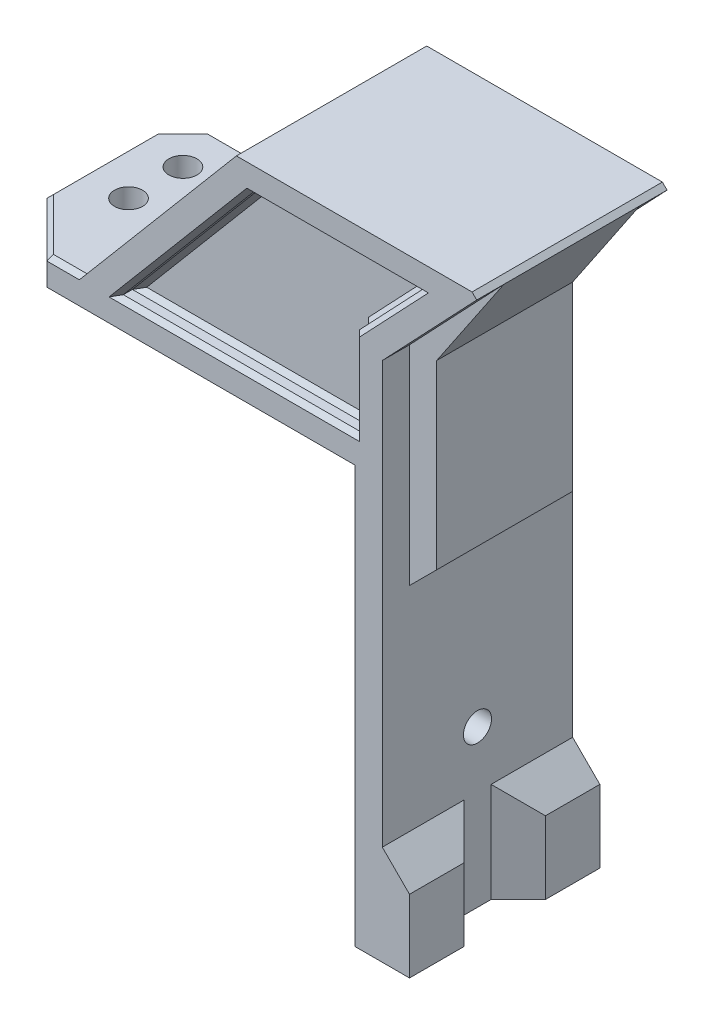
SolidWorks part; units mm, degrees
ref_plane "Front Plane" through (0, 0, 0) normal (0, 0, 1) x (1, 0, 0)
ref_plane "Top Plane" through (0, 0, 0) normal (0, 1, 0) x (1, 0, 0)
ref_plane "Right Plane" through (0, 0, 0) normal (1, 0, 0) x (0, 0, -1)
sketch "Sketch1" plane through (0, 0, 0) normal (1, 0, 0) x (0, 0, -1)
  line L0 (0, 0) -> (0, 46)
  line L1 (0, 0) -> (21, 0)
  line L2 (21, 0) -> (21, 46)
  line L3 (21, 46) -> (0, 46)
  dimension "D1" = 46
  dimension "D2" = 21
extrude "Boss-Extrude1" add sketch "Sketch1" along normal blind 3
sketch "Sketch2" plane through (3, 0, 0) normal (1, 0, 0) x (0, 0, -1)
  line L1 (0, 0) -> (6, 0)
  line L2 (0, 0) -> (0, 8)
  line L3 (0, 8) -> (6, 8)
  line L4 (6, 0) -> (6, 8)
  line L5 (21, 0) -> (15, 0)
  line L6 (21, 0) -> (21, 8)
  line L7 (21, 8) -> (15, 8)
  line L8 (15, 0) -> (15, 8)
  dimension "D1" = 6
  dimension "D2" = 8
  dimension "D3" = 6
extrude "Boss-Extrude2" add sketch "Sketch2" along normal blind 3
chamfer "Chamfer1" distance 3 angle 45 2 edges at (3, 4, -15)
sketch "Sketch3" plane through (0, 0, 0) normal (0, 0, 1) x (1, 0, 0)
  line L0 (0, 46) -> (-30, 46)
  line L1 (3, 46) -> (3, 69) construction
  line L2 (-30, 69) -> (-13.1, 69) construction
  line L3 (-30, 46) -> (-30, 49)
  line L4 (-30, 49) -> (-13.1, 69)
  line L5 (-13.1, 69) -> (13.9, 69)
  line L6 (13.9, 69) -> (3, 57.5)
  line L7 (3, 57.5) -> (3, 46)
  line L8 (0, 46) -> (3, 46)
  dimension "D1" = 30
  dimension "D2" = 23
  dimension "D3" = 16.9
  dimension "D4" = 3
  dimension "D5" = 27
extrude "Boss-Extrude3" add sketch "Sketch3" against normal up to surface (21 mm away) contours L4 L5 L6 L7 L8 L0 L3 up to face at (3, 18, -21)
chamfer "Chamfer2" distance 3 angle 45 2 edges at (3, 8, -16.5)
chamfer "Chamfer3" distance 1 angle 45 1 edges at (13.9, 69, -10.5) first distance on face at (0.4, 69, -10.5)
sketch "Sketch4" plane through (3, 0, 0) normal (1, 0, 0) x (0, 0, -1)
  line L0 (21, 57.5) -> (0, 57.5) construction
  line L1 (3, 57.5) -> (18, 57.5)
  line L2 (3, 57.5) -> (3, 37.5)
  line L3 (3, 37.5) -> (18, 37.5)
  line L4 (18, 57.5) -> (18, 37.5)
  line L5 (0, 57.5) -> (0, 11) construction
  line L6 (21, 11) -> (21, 57.5) construction
  dimension "D1" = 3
  dimension "D2" = 3
  dimension "D3" = 20
extrude "Boss-Extrude4" add sketch "Sketch4" along normal blind 3
sketch "Sketch5" plane through (0, 0, -3) normal (0, 0, 1) x (1, 0, 0)
  line L0 (6, 57.5) -> (13.4134, 68.4866)
  line L1 (6, 57.5) -> (3, 57.5)
  line L11 (3, 57.5) -> (13.4134, 68.4866)
  line L12 (13.4134, 68.4866) -> (12.9, 69)
  line L13 (12.9, 69) -> (-13.1, 69)
  line L14 (-13.1, 69) -> (-30, 49)
  line L15 (-30, 49) -> (-30, 46)
  line L16 (-30, 46) -> (0, 46)
  line L17 (0, 46) -> (0, 0)
  line L18 (0, 0) -> (6, 0)
  line L19 (6, 0) -> (6, 8)
  line L20 (6, 8) -> (3, 11)
  line L21 (3, 11) -> (3, 57.5)
  line L22 (3, 57.5) -> (13.4134, 68.4866)
  line L23 (13.4134, 68.4866) -> (12.9, 69)
  line L24 (12.9, 69) -> (-13.1, 69)
  line L25 (-13.1, 69) -> (-30, 49)
  line L26 (-30, 49) -> (-30, 46)
  line L27 (-30, 46) -> (0, 46)
  line L28 (0, 46) -> (0, 0)
  line L29 (0, 0) -> (6, 0)
  line L30 (6, 0) -> (6, 8)
  line L31 (6, 8) -> (3, 11)
  line L32 (3, 11) -> (3, 57.5)
  line M15 (6, 57.5) -> (3, 57.5)
  dimension "D1" = 0
extrude "Boss-Extrude5" add sketch "Sketch5" against normal up to surface (15 mm away) contours L22 L0 M15 region at (7.4711, 61.1622, -3) up to face at (4.5, 47.5, -18)
chamfer "Chamfer4" distance 3 angle 45 1 edges at (3, 37.5, -10.5)
sketch "Sketch7" plane through (3, 0, 0) normal (1, 0, 0) x (0, 0, -1)
  line L0 (10.5, 0) -> (10.5, 34.5) construction
  line L1 (9, 0) -> (12, 0) construction
  line L2 (18, 34.5) -> (3, 34.5) construction
  circle A0 centre (10.5, 17.25) radius 1.55
  dimension "D1" = 3.1
extrude "Cut-Extrude1" cut sketch "Sketch7" against normal up to next
sketch "Sketch9" plane through (-30, 0, 0) normal (-1, 0, 0) x (0, 0, 1)
  line L4 (0, 49) -> (-21, 49)
  line L5 (-21, 49) -> (-21, 46)
  line L6 (-21, 46) -> (0, 46)
  line L7 (0, 46) -> (0, 49)
  line L8 (0, 49) -> (-21, 49)
  line L9 (-21, 49) -> (-21, 46)
  line L10 (-21, 46) -> (0, 46)
  line L11 (0, 46) -> (0, 49)
  dimension "D1" = 0
extrude "Boss-Extrude6" add sketch "Sketch9" along normal blind 10
sketch "Sketch10" plane through (0, 49, 0) normal (0, 1, 0) x (1, 0, 0)
  line L0 (-35, 21) -> (-35, 0) construction
  line L1 (-40, 21) -> (-30, 21) construction
  line L2 (-40, 0) -> (-30, 0) construction
  circle A0 centre (-35, 16) radius 1.55
  circle A1 centre (-35, 10) radius 1.55
  dimension "D1" = 3.1
  dimension "D2" = 3.1
  dimension "D3" = 6
  dimension "D4" = 10
extrude "Cut-Extrude2" cut sketch "Sketch10" against normal up to next
chamfer "Chamfer5" distance 3 angle 45 1 edges at (-40, 47.5, -21)
chamfer "Chamfer7" distance 6 angle 45 1 edges at (-40, 47.5, 0)
chamfer "Chamfer6" distance 0.5 angle 45 5 edges at (-40, 49, -12) (-32, 49, 0) (-33.5, 49, -21) (-38.5, 49, -19.5) (-37, 49, -3)
sketch "Sketch11" plane through (0, 0, 0) normal (0, 0, 1) x (1, 0, 0)
  line L0 (-30.4225, 48.5) -> (-13.1, 69)
  line L1 (-13.1, 69) -> (12.9, 69)
  line L2 (12.9, 69) -> (13.4134, 68.4866)
  line L3 (13.4134, 68.4866) -> (3, 57.5)
  line L4 (3, 57.5) -> (3, 46)
  line L5 (3, 57.5) -> (3, 11) construction
  line L6 (3, 46) -> (-30.4225, 46)
  line L7 (0, 46) -> (-34, 46) construction
  line L8 (-30.4225, 46) -> (-30.4225, 48.5)
  line L9 (-26.0724, 49) -> (-11.7074, 66)
  line L10 (-11.7074, 66) -> (6.9231, 66)
  line L11 (6.9231, 66) -> (6.9231, 66)
  line L12 (6.9231, 66) -> (0, 58.6958)
  line L13 (0, 58.6958) -> (0, 49)
  line L14 (0, 49) -> (-26.0724, 49)
  line L15 (-26.0724, 49) -> (-26.0724, 49)
  dimension "D1" = 3
extrude "Cut-Extrude3" cut sketch "Sketch11" against normal blind 2 contours L14 L13 L12 L10 L9 region at (-9.0091, 56.944, 0)
chamfer "Chamfer8" distance 0.5 angle 45 10 edges at (-2.3922, 66, -2) (3.4615, 62.3479, -2) (0, 53.8479, -2) (-18.8899, 57.5, -2) (-13.0362, 49, -2) (-2.3922, 66, 0) (3.4615, 62.3479, 0) (0, 53.8479, 0) (-13.0362, 49, 0) (-18.8899, 57.5, 0)
